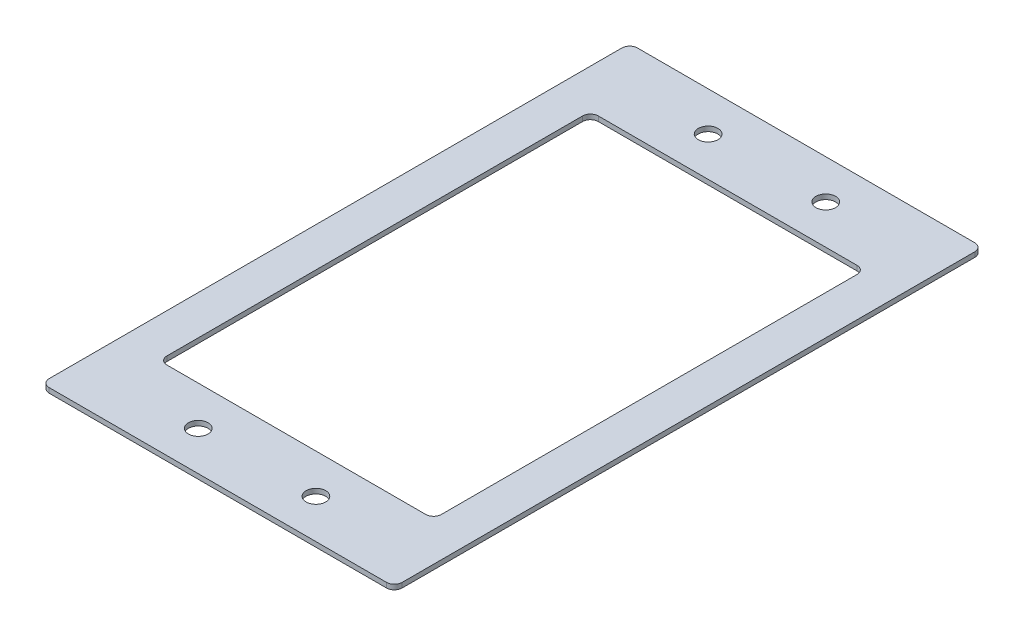
SolidWorks part; units mm, degrees
ref_plane "Front Plane" through (0, 0, 0) normal (0, 0, 1) x (1, 0, 0)
ref_plane "Top Plane" through (0, 0, 0) normal (0, 1, 0) x (1, 0, 0)
ref_plane "Right Plane" through (0, 0, 0) normal (1, 0, 0) x (0, 0, -1)
sketch "Sketch1" plane through (0, 0, 0) normal (0, 1, 0) x (1, 0, 0)
  line L1 (57.15, -95.25) -> (-57.15, -95.25)
  line L2 (57.15, -95.25) -> (57.15, 95.25)
  line L3 (57.15, 95.25) -> (-57.15, 95.25)
  line L4 (-57.15, -95.25) -> (-57.15, 95.25)
  line L5 (57.15, -95.25) -> (-57.15, 95.25) construction
  line L6 (57.15, 95.25) -> (-57.15, -95.25) construction
  line L7 (44.45, -69.85) -> (-44.45, -69.85)
  line L8 (44.45, -69.85) -> (44.45, 69.85)
  line L9 (44.45, 69.85) -> (-44.45, 69.85)
  line L10 (-44.45, -69.85) -> (-44.45, 69.85)
  line L11 (44.45, -69.85) -> (-44.45, 69.85) construction
  line L12 (44.45, 69.85) -> (-44.45, -69.85) construction
  point P0 (0, 0)
  point P6 (0, 0)
  dimension "D1" = 114.3
  dimension "D2" = 190.5
  dimension "D3" = 12.7
  dimension "D4" = 25.4
extrude "Boss-Extrude1" add sketch "Sketch1" along normal blind 1.5875
sketch "Sketch2" plane through (0, 1.5875, 0) normal (0, 1, 0) x (1, 0, 0)
  line L0 (-57.15, -95.25) -> (57.15, -95.25) construction
  line L1 (57.15, -95.25) -> (57.15, 95.25) construction
  line L3 (0, 0) -> (38.7987, 0) construction
  line L4 (38.7987, 0) -> (-37.1207, 0) construction
  line L5 (0, 0) -> (0, -35.6688) construction
  circle A0 centre (19.05, -82.55) radius 3.175
  circle A1 centre (19.05, 82.55) radius 3.175
  circle A2 centre (-19.05, -82.55) radius 3.175
  circle A3 centre (-19.05, 82.55) radius 3.175
  dimension "D1" = 12.7
  dimension "D2" = 6.35
  dimension "D3" = 38.1
extrude "Cut-Extrude1" cut sketch "Sketch2" against normal blind 4.7625
fillet "Fillet1" radius 2.54 4 edges at (44.45, 0.7937, -69.85) (-44.45, 0.7937, -69.85) (-44.45, 0.7937, 69.85) (44.45, 0.7937, 69.85)
fillet "Fillet2" radius 2.54 4 edges at (-57.15, 0.7937, 95.25) (-57.15, 0.7937, -95.25) (57.15, 0.7937, -95.25) (57.15, 0.7937, 95.25)
